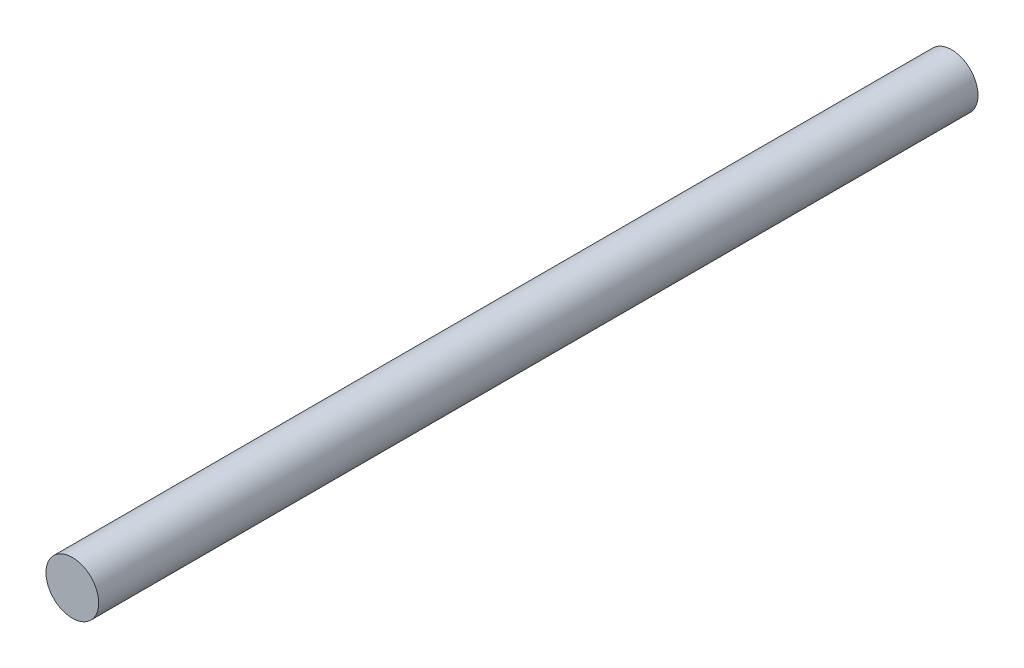
SolidWorks part; units mm, degrees
ref_plane "Front Plane" through (0, 0, 0) normal (0, 0, 1) x (1, 0, 0)
ref_plane "Top Plane" through (0, 0, 0) normal (0, 1, 0) x (1, 0, 0)
ref_plane "Right Plane" through (0, 0, 0) normal (1, 0, 0) x (0, 0, -1)
sketch "Sketch1" plane through (0, 0, 0) normal (0, 0, 1) x (1, 0, 0)
  circle A0 centre (0, 0) radius 150
  circle A1 centre (0, 0) radius 250 construction
  dimension "D1" = 300
extrude "Boss-Extrude1" add sketch "Sketch1" along normal blind 5000
ref_axis "Axis1" through (0, 0, 5000) along (0, 0, -1)
